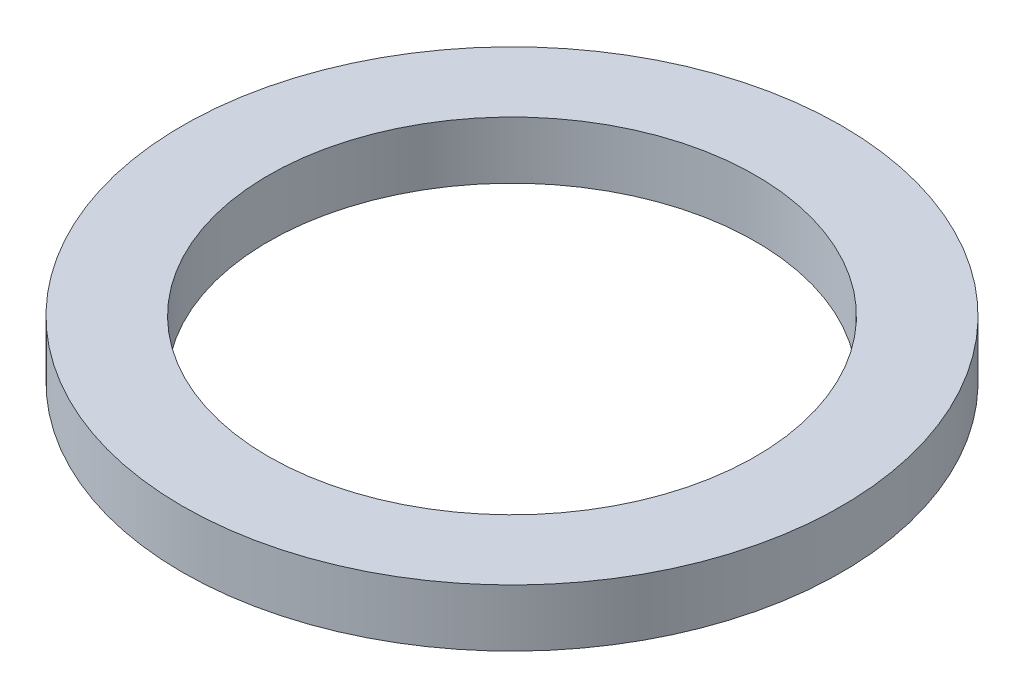
SolidWorks part; units mm, degrees
ref_plane "Front Plane" through (0, 0, 0) normal (0, 0, 1) x (1, 0, 0)
ref_plane "Top Plane" through (0, 0, 0) normal (0, 1, 0) x (1, 0, 0)
ref_plane "Right Plane" through (0, 0, 0) normal (1, 0, 0) x (0, 0, -1)
sketch "Sketch1" plane through (0, 0, 0) normal (0, 1, 0) x (1, 0, 0)
  circle A0 centre (0, 0) radius 57.5
  dimension "FLANGE_OD" = 115
extrude "Boss-Extrude1" add sketch "Sketch1" along normal blind 10
sketch "Sketch2" plane through (0, 0, 0) normal (0, 1, 0) x (1, 0, 0)
  circle A0 centre (0, 0) radius 42.5
  dimension "BORE_D" = 85
extrude "Cut-Extrude1" cut sketch "Sketch2" along normal through all
sketch "Sketch3" plane through (0, 10, 0) normal (0, 1, 0) x (1, 0, 0)
  circle A0 centre (0, 0) radius 23.3422 construction
  circle A1 centre (-23.3422, 0) radius 2.4392
  dimension "BOLT_D" = 4.8785
  dimension "BOLT_PCD" = 46.6843
extrude "Cut-Extrude2" cut sketch "Sketch3" against normal blind 8.7274 rebuild error yes
pattern_circular "CirPattern1" count 4 over 360 rebuild error yes
